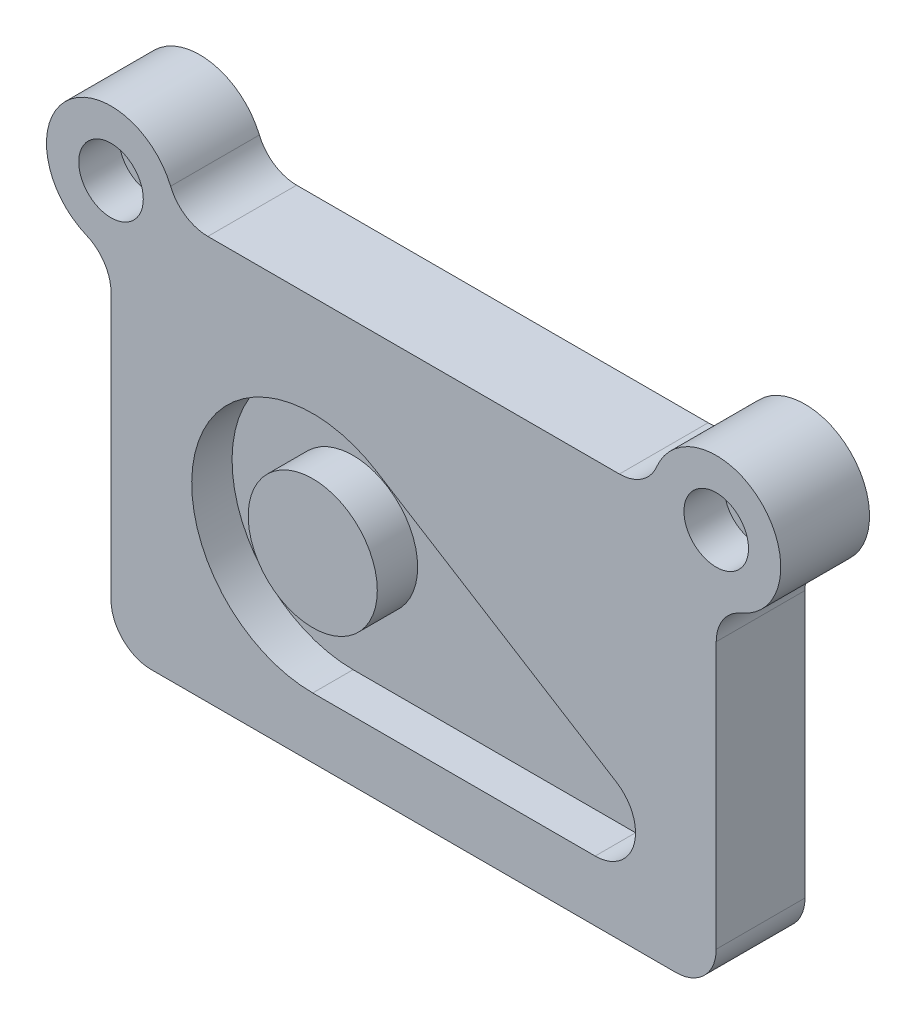
SolidWorks part; units mm, degrees
material "1060 Alloy"
ref_plane "Front Plane" through (0, 0, 0) normal (0, 0, 1) x (1, 0, 0)
ref_plane "Top Plane" through (0, 0, 0) normal (0, 1, 0) x (1, 0, 0)
ref_plane "Right Plane" through (0, 0, 0) normal (1, 0, 0) x (0, 0, -1)
sketch "Sketch4" plane through (0, 0, 0) normal (0, 0, 1) x (1, 0, 0)
  line L0 (65.8491, 70.4717) -> (125.283, 33.4906)
  line L1 (126, 100) -> (24, 100)
  line L2 (150, 76) -> (150, 10)
  line L3 (140, 0) -> (10, 0)
  line L4 (0, 76) -> (0, 10)
  line L5 (50, 15) -> (120, 15)
  arc A0 (14.7692, 106.1538) -> (-6.1538, 85.2308) centre (0, 100) ccw
  arc A1 (24, 100) -> (14.7692, 106.1538) centre (24, 110) cw
  arc A2 (156.1538, 85.2308) -> (135.2308, 106.1538) centre (150, 100) ccw
  arc A3 (135.2308, 106.1538) -> (126, 100) centre (126, 110) cw
  arc A4 (150, 76) -> (156.1538, 85.2308) centre (160, 76) cw
  arc A5 (140, 0) -> (150, 10) centre (140, 10) ccw
  arc A6 (0, 10) -> (10, 0) centre (10, 10) ccw
  arc A7 (-6.1538, 85.2308) -> (0, 76) centre (-10, 76) cw
  circle A8 centre (50, 45) radius 16
  arc A9 (65.8491, 70.4717) -> (50, 15) centre (50, 45) ccw
  arc A10 (120, 15) -> (125.283, 33.4906) centre (120, 25) ccw
  circle A11 centre (0, 100) radius 8
  circle A12 centre (150, 100) radius 8
  circle A13 centre (0, 100) radius 3
  circle A14 centre (150, 100) radius 3
  dimension "D1" = 10
extrude "Extrude1" add sketch "Sketch4" against normal blind 22 contours L3 A6 L4 A7 A0 A1 L1 A3 A2 A4 L2 A5 | A13 | A14
extrude "Cut-Extrude1" cut sketch "Sketch4<3>" against normal blind 10 from surface contours A9 L5 A10 L0 | A8 starting at face at (153, 100, 0)
sketch "Sketch4<3>" plane through (0, 0, 0) normal (0, 0, 1) x (1, 0, 0) same geometry as "Sketch4"
extrude "Cut-Extrude2" cut sketch "Sketch4<4>" against normal blind 10 from surface contours A11 | A12 starting at face at (75, 65.0782, 0)
sketch "Sketch4<4>" plane through (0, 0, 0) normal (0, 0, 1) x (1, 0, 0) same geometry as "Sketch4"
